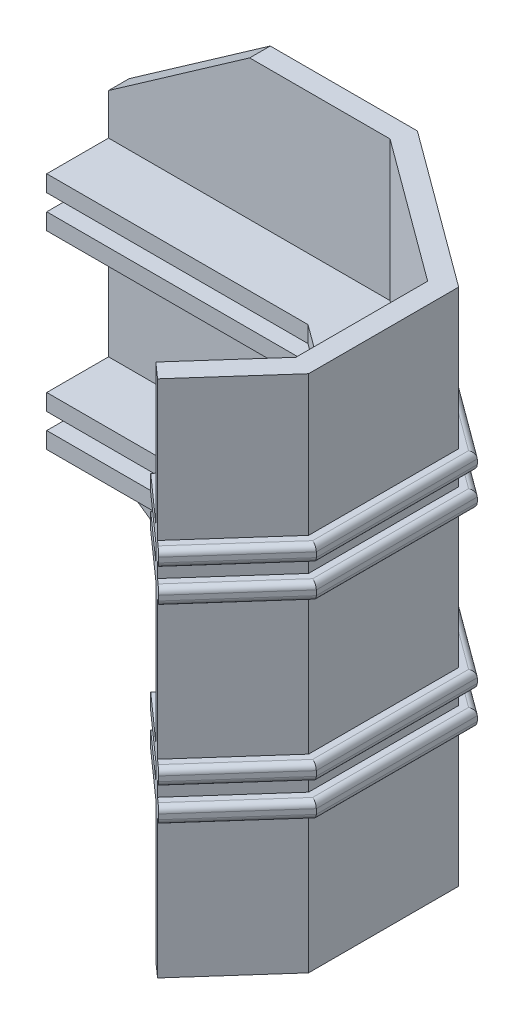
SolidWorks part; units mm, degrees
ref_plane "前视基准面" through (0, 0, 0) normal (0, 0, 1) x (1, 0, 0)
ref_plane "上视基准面" through (0, 0, 0) normal (0, 1, 0) x (1, 0, 0)
ref_plane "右视基准面" through (0, 0, 0) normal (1, 0, 0) x (0, 0, -1)
sketch "草图1" plane through (0, 0, 0) normal (0, 1, 0) x (1, 0, 0)
  line L0 (0, -8) -> (0, 8)
  line L1 (0, 8) -> (-17.2409, 20.6772)
  line L2 (0, -8) -> (-8, -17)
  line L3 (2.5, -8.9505) -> (-6.1315, -18.6609)
  line L4 (2.5, -8.9505) -> (2.5, 9.2648)
  line L5 (2.5, 9.2648) -> (-16.4207, 23.1772)
  line L6 (-6.1315, -18.6609) -> (-8, -17)
  line L7 (-17.2409, 20.6772) -> (-51.4207, 20.6772)
  line L8 (-51.4207, 23.1772) -> (-16.4207, 23.1772)
  line L9 (2.5, 9.2648) -> (-15.76, 22.6913) construction
  line L10 (-51.4207, 23.1772) -> (-51.4207, 20.6772)
  dimension "D1" = 16
  dimension "D2" = 21.4
  dimension "D3" = 126.327
  dimension "D4" = 9
  dimension "D5" = 8
  dimension "D7" = 2.5
  dimension "D8" = 35
  dimension "D6" = 2.5
extrude "凸台-拉伸1" add sketch "草图1" along normal blind 31.5 and the other way blind 31.5
chamfer "倒角1" distance 12 angle 55 2 edges at (-51.4207, -31.5, -21.9272) (-51.4207, 31.5, -21.9272) first distance on face at (-51.4207, 0, -21.9272)
ref_plane "基准面1" through (0, 10.5, 0) normal (0, 1, 0) x (1, 0, 0)
sketch "草图4" plane through (0, 10.5, 0) normal (0, 1, 0) x (1, 0, 0)
  line L0 (2.5, 9.2648) -> (-16.4207, 23.1772) construction
  line L1 (2.5, 9.2648) -> (-16.4207, 23.1772)
  line L2 (-6.1315, -18.6609) -> (2.5, -8.9505) construction
  line L3 (2.5, -8.9505) -> (2.5, 9.2648) construction
  line L4 (-16.4207, 23.1772) -> (-34.283, 23.1772) construction
  line L5 (-51.4207, 23.1772) -> (-34.283, 23.1772) construction
  line L6 (-6.1315, -18.6609) -> (2.5, -8.9505)
  line L7 (2.5, -8.9505) -> (2.5, 9.2648)
  line L8 (-16.4207, 23.1772) -> (-34.283, 23.1772)
  line L9 (-51.4207, 23.1772) -> (-34.283, 23.1772)
  line L10 (-5.0104, -19.6575) -> (4, -9.5208)
  line L11 (4, -9.5208) -> (4, 10.0238)
  line L12 (4, 10.0238) -> (-15.9286, 24.6772)
  line L13 (-15.9286, 24.6772) -> (-34.283, 24.6772)
  line L14 (-51.4207, 24.6772) -> (-34.283, 24.6772)
  dimension "D1" = 1.5
extrude "拉伸-薄壁1" add sketch "草图4" against normal blind 2 thin thin type one direction wall 10
ref_plane "基准面2" through (0, 14.5, 0) normal (0, 1, 0) x (1, 0, 0)
sketch "草图5" plane through (0, 14.5, 0) normal (0, 1, 0) x (1, 0, 0)
  line L0 (-6.1315, -18.6609) -> (2.5, -8.9505) construction
  line L1 (2.5, -8.9505) -> (2.5, 9.2648) construction
  line L2 (2.5, 9.2648) -> (-16.4207, 23.1772) construction
  line L3 (-16.4207, 23.1772) -> (-34.283, 23.1772) construction
  line L4 (-51.4207, 23.1772) -> (-34.283, 23.1772) construction
  line L5 (-6.1315, -18.6609) -> (2.5, -8.9505)
  line L6 (2.5, -8.9505) -> (2.5, 9.2648)
  line L7 (2.5, 9.2648) -> (-16.4207, 23.1772)
  line L8 (-16.4207, 23.1772) -> (-34.283, 23.1772)
  line L9 (-51.4207, 23.1772) -> (-34.283, 23.1772)
  line L10 (-5.0104, -19.6575) -> (4, -9.5208)
  line L11 (4, -9.5208) -> (4, 10.0238)
  line L12 (4, 10.0238) -> (-15.9286, 24.6772)
  line L13 (-15.9286, 24.6772) -> (-34.283, 24.6772)
  line L14 (-51.4207, 24.6772) -> (-34.283, 24.6772)
  dimension "D1" = 1.5
extrude "拉伸-薄壁2" add sketch "草图5" against normal blind 2 thin thin type one direction wall 10
fillet "圆角1" radius 0.7 16 edges at (-0.5052, 8.5, 14.5891) (4, 8.5, -0.2515) (-5.9643, 8.5, -17.3505) (-33.6747, 8.5, -24.6772) (-0.5052, 10.5, 14.5891) (4, 10.5, -0.2515) (-5.9643, 10.5, -17.3505) (-33.6747, 10.5, -24.6772) (-33.6747, 12.5, -24.6772) (-5.9643, 12.5, -17.3505) (4, 12.5, -0.2515) (-0.5052, 12.5, 14.5891) (-0.5052, 14.5, 14.5891) (4, 14.5, -0.2515) (-5.9643, 14.5, -17.3505) (-33.6747, 14.5, -24.6772)
mirror "镜向1" about plane through (0, 0, 0) normal (0, 1, 0) of "圆角1", "拉伸-薄壁2", "拉伸-薄壁1"
